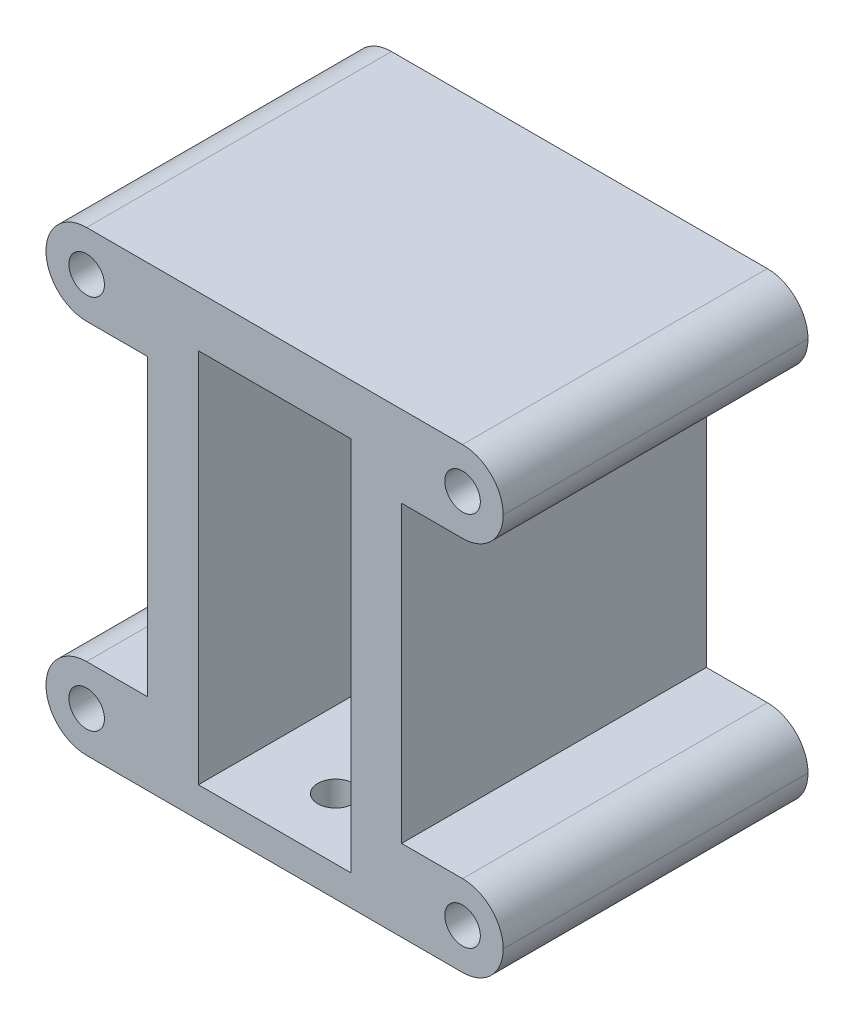
SolidWorks part; units mm, degrees
ref_plane "Alzado" through (0, 0, 0) normal (0, 0, 1) x (1, 0, 0)
ref_plane "Planta" through (0, 0, 0) normal (0, 1, 0) x (1, 0, 0)
ref_plane "Vista lateral" through (0, 0, 0) normal (1, 0, 0) x (0, 0, -1)
sketch "Croquis3" plane through (0, 0, 0) normal (0, 0, 1) x (1, 0, 0)
  line L1 (-12.0157, -24) -> (2.9843, -24)
  line L2 (-12.0157, -24) -> (-12.0157, 13)
  line L3 (-12.0157, 13) -> (2.9843, 13)
  line L4 (2.9843, -24) -> (2.9843, 13)
  line L7 (-17.0157, -27) -> (7.9843, -27)
  line L8 (-17.0157, -27) -> (-17.0157, 18)
  line L9 (-17.0157, 18) -> (7.9843, 18)
  line L10 (7.9843, -27) -> (7.9843, 18)
  point P0 (0, 0)
  point P6 (0, 0)
  dimension "D1" = 45
  dimension "D2" = 25
  dimension "D3" = 5
  dimension "D4" = 5
  dimension "D5" = 5
  dimension "D6" = 3
extrude "Saliente-Extruir1" add sketch "Croquis3" along normal blind 30
ref_plane "Plano1" through (-4.5157, 0, 0) normal (-1, 0, 0) x (0, 0, 1)
sketch "Croquis4" plane through (-17.0157, 0, 0) normal (-1, 0, 0) x (0, 0, 1)
  line L0 (15, 18) -> (15, -27) construction
  line L1 (30, 18) -> (0, 18) construction
  line L2 (30, -27) -> (0, -27) construction
  line L3 (0, 10) -> (30, 10)
  line L21 (30, 18) -> (30, 10)
  line L25 (0, 10) -> (0, 18)
  line L26 (0, 18) -> (30, 18)
  line L28 (0, -27) -> (30, -27)
  line L29 (0, -27) -> (0, -19)
  line L30 (0, -19) -> (30, -19)
  line L31 (30, -27) -> (30, -19)
  line L32 (30, 18) -> (30, -27) construction
  dimension "D1" = 8
  dimension "D3" = 8
  dimension "D4" = 8
extrude "Saliente-Extruir2" add sketch "Croquis4" along normal blind 10
sketch "Croquis5" plane through (0, 0, 30) normal (0, 0, 1) x (1, 0, 0)
  line L0 (-17.0157, 10) -> (-17.0157, -19) construction
  line L1 (-27.0157, -27) -> (7.9843, -27) construction
  line L2 (-27.0157, 10) -> (-17.0157, 10) construction
  line L3 (-17.0157, 10) -> (-17.0157, -19) construction
  circle A0 centre (-23.0157, 14) radius 1.75
  circle A2 centre (-23.0157, -23) radius 1.75
  dimension "D1" = 3.5
  dimension "D2" = 3.5
  dimension "D3" = 6
  dimension "D4" = 6
  dimension "D5" = 4
  dimension "D6" = 4
extrude "Cortar-Extruir1" cut sketch "Croquis5" against normal through all both and the other way through all
fillet "Redondeo1" radius 4 4 edges at (-27.0157, -27, 15) (-27.0157, -19, 15) (-27.0157, 10, 15) (-27.0157, 18, 15)
mirror "Simetría1" about plane through (-4.5157, 0, 0) normal (-1, 0, 0) of "Saliente-Extruir2", "Redondeo1", "Cortar-Extruir1"
sketch "Croquis7" plane through (0, -24, 0) normal (0, 1, 0) x (1, 0, 0)
  line L0 (-27.0157, -15) -> (17.9843, -15) construction
  line L3 (-27.0157, -30) -> (-27.0157, 0) construction
  line L4 (17.9843, 0) -> (17.9843, -30) construction
  line L6 (-4.5157, 0) -> (-4.5157, -30) construction
  line L8 (13.9843, -30) -> (-23.0157, -30) construction
  line L13 (13.9843, 0) -> (-23.0157, 0) construction
  circle A1 centre (-4.5157, -24) radius 1.75
  circle A3 centre (-4.5157, -15) radius 1.75
  circle A4 centre (-4.5157, -6) radius 1.75
  dimension "D2" = 3.5
  dimension "D3" = 6
  dimension "D5" = 6
  dimension "D10" = 3.5
  dimension "D12" = 3.5
extrude "Cortar-Extruir2" cut sketch "Croquis7" against normal through all
